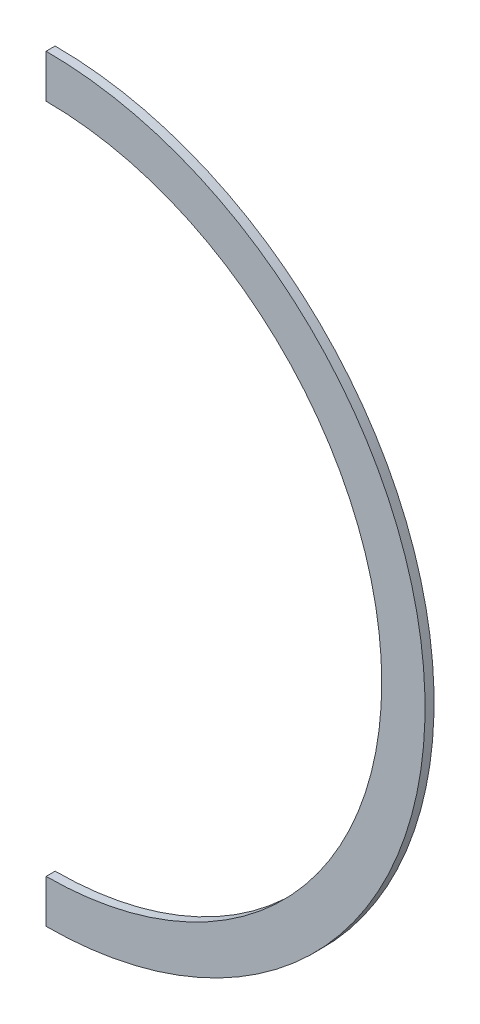
SolidWorks part; units mm, degrees
material "Balsa"
ref_plane "Front Plane" through (0, 0, 0) normal (0, 0, 1) x (1, 0, 0)
ref_plane "Top Plane" through (0, 0, 0) normal (0, 1, 0) x (1, 0, 0)
ref_plane "Right Plane" through (0, 0, 0) normal (1, 0, 0) x (0, 0, -1)
sketch "Sketch1" plane through (0, 0, 0) normal (0, 0, 1) x (1, 0, 0)
  line L0 (0, -110.0909) -> (0, -70.6286) construction
  line L1 (0, 0) -> (0, 245.1538) construction
  line L2 (0, 0) -> (0, 631.6453) construction
  line L3 (-120.188, -34.2725) -> (-93.2472, -61.2132)
  line L4 (0, 0) -> (-284.8905, 0) construction
  line L5 (-93.2472, -61.2132) -> (-94.2927, -70.7977)
  line L8 (-93.2472, -61.2132) -> (-57.7675, -96.693) construction
  arc A0 (-57.7675, -96.693) -> (-120.188, -34.2725) centre (0, 23.495) ccw
  arc A2 (-120.188, -34.2725) -> (-57.7675, -96.693) centre (0, 23.495) ccw construction
  arc A3 (-94.2927, -70.7977) -> (-57.7675, -96.693) centre (0, 23.495) ccw
  point P2 (0, 156.7839)
  point P3 (0, -109.8059)
  point P15 (-93.2472, -61.2132)
  dimension "D1" = 266.5898
  dimension "D2" = 266.7
  dimension "D3" = 23.495
  dimension "D5" = 109.22
  dimension "D6" = 45
  dimension "D7" = 38.1
extrude "Boss-Extrude1" add sketch "Sketch1" along normal mid plane 3.175
sketch "Sketch2" plane through (0, 0, 1.5875) normal (0, 0, 1) x (1, 0, 0)
  line L4 (-77.3048, -55.603) -> (-78.3203, -64.9126)
  line L5 (-107.5191, -25.3887) -> (-77.3048, -55.603)
  line L6 (-77.3048, -55.603) -> (-78.3203, -64.9126)
  line L7 (-107.5191, -25.3887) -> (-77.3048, -55.603)
  arc A2 (-78.3203, -64.9126) -> (-107.5191, -25.3887) centre (0, 23.495) ccw
  arc A3 (-78.3203, -64.9126) -> (-107.5191, -25.3887) centre (0, 23.495) ccw
  dimension "D1" = 15.24
extrude "Cut-Extrude1" cut sketch "Sketch2" against normal up to surface (3.175 mm away) up to face at (-30.5678, -4.3762, -1.5875)
fillet "Fillet1" radius 8.89 6 edges at (-107.5191, -25.3887, 0) (-120.188, -34.2725, 0) (-94.2927, -70.7977, 0) (-93.2472, -61.2132, 0) (-77.3048, -55.603, 0) (-78.3203, -64.9126, 0)
sketch "Sketch3" plane through (0, 0, 0) normal (1, 0, 0) x (0, 0, -1)
  line L1 (-107.0531, 227.715) -> (127.3903, 227.715)
  line L2 (-107.0531, 227.715) -> (-107.0531, -194.8481)
  line L3 (-107.0531, -194.8481) -> (127.3903, -194.8481)
  line L4 (127.3903, 227.715) -> (127.3903, -194.8481)
extrude "Cut-Extrude2" cut sketch "Sketch3" against normal through all
